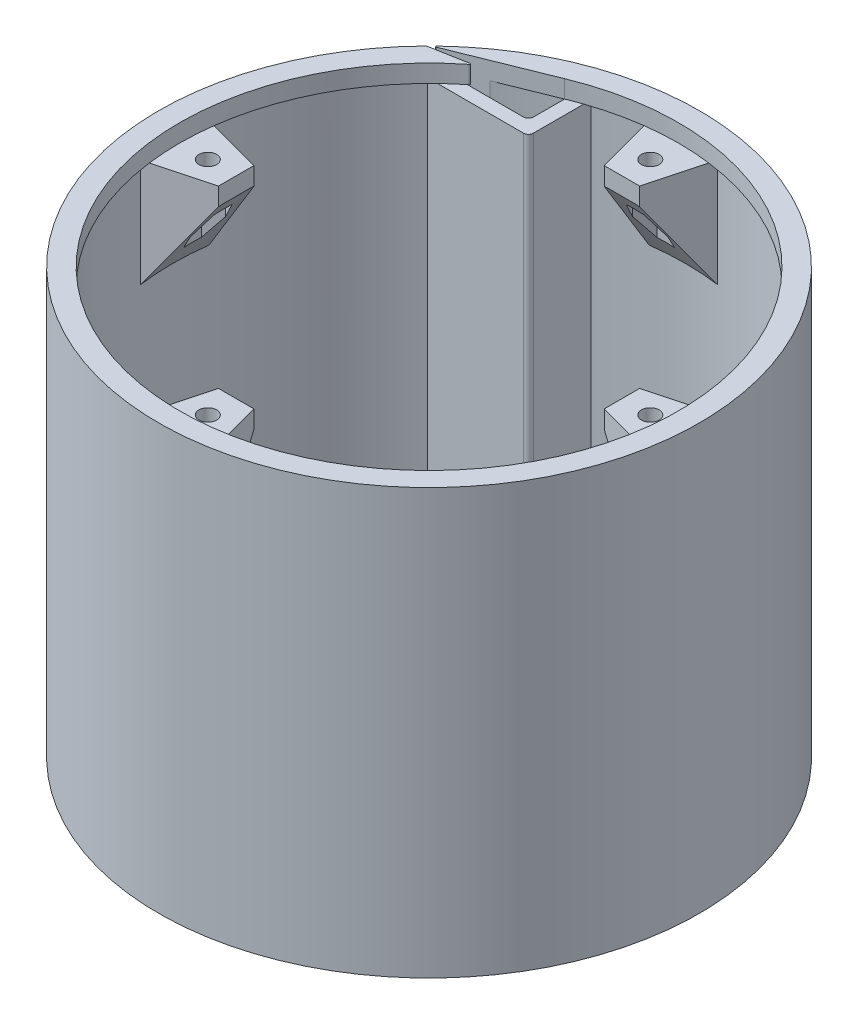
SolidWorks part; units mm, degrees
ref_plane "Front Plane" through (0, 0, 0) normal (0, 0, 1) x (1, 0, 0)
ref_plane "Top Plane" through (0, 0, 0) normal (0, 1, 0) x (1, 0, 0)
ref_plane "Right Plane" through (0, 0, 0) normal (1, 0, 0) x (0, 0, -1)
sketch "Sketch1" plane through (0, 0, 0) normal (0, 1, 0) x (1, 0, 0)
  line L0 (0, 0) -> (0, 89.535) construction
  circle A0 centre (0, 0) radius 89.535
  circle A1 centre (0, 79.375) radius 3.175
  circle A2 centre (20.5438, 76.6704) radius 3.175
  circle A3 centre (39.6875, 68.7408) radius 3.175 [skipped]
  circle A4 centre (56.1266, 56.1266) radius 3.175 [skipped]
  circle A5 centre (68.7408, 39.6875) radius 3.175 [skipped]
  circle A6 centre (76.6704, 20.5438) radius 3.175
  circle A7 centre (79.375, 0) radius 3.175
  circle A8 centre (76.6704, -20.5438) radius 3.175
  circle A9 centre (68.7408, -39.6875) radius 3.175 [skipped]
  circle A10 centre (56.1266, -56.1266) radius 3.175 [skipped]
  circle A11 centre (39.6875, -68.7408) radius 3.175 [skipped]
  circle A12 centre (20.5438, -76.6704) radius 3.175
  circle A13 centre (0, -79.375) radius 3.175
  circle A14 centre (-20.5438, -76.6704) radius 3.175
  circle A15 centre (-39.6875, -68.7408) radius 3.175 [skipped]
  circle A16 centre (-56.1266, -56.1266) radius 3.175 [skipped]
  circle A17 centre (-68.7408, -39.6875) radius 3.175 [skipped]
  circle A18 centre (-76.6704, -20.5438) radius 3.175
  circle A19 centre (-79.375, 0) radius 3.175
  circle A20 centre (-76.6704, 20.5438) radius 3.175
  circle A21 centre (-68.7408, 39.6875) radius 3.175 [skipped]
  circle A22 centre (-56.1266, 56.1266) radius 3.175 [skipped]
  circle A23 centre (-39.6875, 68.7408) radius 3.175 [skipped]
  circle A24 centre (-20.5438, 76.6704) radius 3.175
  circle A25 centre (0, 0) radius 97.0209
  circle A26 centre (0, 0) radius 92.0209
  point P55 (0, 0)
  dimension "D1" = 179.07
  dimension "D2" = 6.35
  dimension "D3" = 79.375
  dimension "D4" = 24
  dimension "D5" = 194.0417
  dimension "D6" = 5
extrude "Boss-Extrude1" add sketch "Sketch1" along normal blind 152.4 contours A25 A26
sketch "Sketch2" plane through (0, 152.4, 0) normal (0, 1, 0) x (1, 0, 0)
  circle A1 centre (0, 0) radius 92.0209
  circle A2 centre (0, 0) radius 92.0209
  circle A3 centre (0, 0) radius 97.0209
  circle A4 centre (0, 0) radius 97.0209
  circle A5 centre (20.5438, 76.6704) radius 3.175
  circle A6 centre (20.5438, 76.6704) radius 3.175
  circle A7 centre (0, 79.375) radius 3.175
  circle A8 centre (0, 79.375) radius 3.175
  circle A9 centre (0, 0) radius 89.535
  circle A10 centre (0, 0) radius 89.535
  circle A11 centre (20.5438, -76.6704) radius 3.175
  circle A12 centre (20.5438, -76.6704) radius 3.175
  circle A13 centre (76.6704, -20.5438) radius 3.175
  circle A14 centre (76.6704, -20.5438) radius 3.175
  circle A15 centre (79.375, 0) radius 3.175
  circle A16 centre (79.375, 0) radius 3.175
  circle A17 centre (76.6704, 20.5438) radius 3.175
  circle A18 centre (76.6704, 20.5438) radius 3.175
  circle A19 centre (-76.6704, 20.5438) radius 3.175
  circle A20 centre (-76.6704, 20.5438) radius 3.175
  circle A21 centre (-79.375, 0) radius 3.175
  circle A22 centre (-79.375, 0) radius 3.175
  circle A23 centre (-76.6704, -20.5438) radius 3.175
  circle A24 centre (-76.6704, -20.5438) radius 3.175
  circle A25 centre (-20.5438, -76.6704) radius 3.175
  circle A26 centre (-20.5438, -76.6704) radius 3.175
  circle A27 centre (0, -79.375) radius 3.175
  circle A28 centre (0, -79.375) radius 3.175
  circle A29 centre (-20.5438, 76.6704) radius 3.175
  circle A30 centre (-20.5438, 76.6704) radius 3.175
  circle M16 centre (0, 0) radius 92.0209
  dimension "D1" = 0
  dimension "D2" = 0
  dimension "D3" = 0
  dimension "D4" = 0
  dimension "D5" = 0
  dimension "D6" = 0
  dimension "D7" = 0
  dimension "D8" = 0
  dimension "D9" = 0
  dimension "D10" = 0
  dimension "D11" = 0
  dimension "D12" = 0
  dimension "D13" = 0
  dimension "D14" = 0
  dimension "D15" = 0
extrude "Boss-Extrude2" add sketch "Sketch2" against normal blind 6.35 contours A10 M16
sketch "Sketch3" plane through (0, 146.05, 0) normal (0, -1, 0) x (1, 0, 0)
  line L0 (0, 89.535) -> (0, 0) construction
  line L1 (-6.35, 69.215) -> (6.35, 69.215)
  line L2 (-12.2417, 91.203) -> (-6.35, 69.215)
  line L3 (6.35, 69.215) -> (12.2417, 91.203)
  circle A1 centre (0, 0) radius 92.0209
  circle A2 centre (0, 0) radius 92.0209
  circle A3 centre (0, 0) radius 97.0209
  circle A4 centre (0, 0) radius 97.0209
  circle A5 centre (20.5438, -76.6704) radius 3.175
  circle A6 centre (20.5438, -76.6704) radius 3.175
  circle A7 centre (0, -79.375) radius 3.175
  circle A8 centre (0, -79.375) radius 3.175
  circle A9 centre (0, 0) radius 89.535
  circle A10 centre (0, 0) radius 89.535
  circle A11 centre (20.5438, 76.6704) radius 3.175
  circle A12 centre (20.5438, 76.6704) radius 3.175
  circle A13 centre (76.6704, 20.5438) radius 3.175
  circle A14 centre (76.6704, 20.5438) radius 3.175
  circle A15 centre (79.375, 0) radius 3.175
  circle A16 centre (79.375, 0) radius 3.175
  circle A17 centre (76.6704, -20.5438) radius 3.175
  circle A18 centre (76.6704, -20.5438) radius 3.175
  circle A19 centre (-76.6704, -20.5438) radius 3.175
  circle A20 centre (-76.6704, -20.5438) radius 3.175
  circle A21 centre (-79.375, 0) radius 3.175
  circle A22 centre (-79.375, 0) radius 3.175
  circle A23 centre (-76.6704, 20.5438) radius 3.175
  circle A24 centre (-76.6704, 20.5438) radius 3.175
  circle A25 centre (-20.5438, 76.6704) radius 3.175
  circle A26 centre (-20.5438, 76.6704) radius 3.175
  circle A27 centre (0, 79.375) radius 3.175
  circle A28 centre (0, 79.375) radius 3.175
  circle A29 centre (-20.5438, -76.6704) radius 3.175
  circle A30 centre (-20.5438, -76.6704) radius 3.175
  circle M20 centre (0, 0) radius 89.535
  circle M21 centre (0, 0) radius 92.0209
  dimension "D16" = 12.7
  dimension "D17" = 6.35
  dimension "D18" = 20.32
  dimension "D19" = 15
  dimension "D20" = 15
  dimension "D1" = 0
  dimension "D2" = 0
  dimension "D3" = 0
  dimension "D4" = 0
  dimension "D5" = 0
  dimension "D6" = 0
  dimension "D7" = 0
  dimension "D8" = 0
  dimension "D9" = 0
  dimension "D10" = 0
  dimension "D11" = 0
  dimension "D12" = 0
  dimension "D13" = 0
  dimension "D14" = 0
  dimension "D15" = 0
extrude "Boss-Extrude3" add sketch "Sketch3" along normal blind 6.35 contours A10 L3 L2 M20 M21 | L0 L2 L1 A28 M20 | A10 L0 A28 L1 L3
pattern_circular "CirPattern1" count 4 every 90 about axis through (0, 0, 0) along (0, 1, 0) of "Boss-Extrude3"
sketch "Sketch4" plane through (0, 0, 0) normal (0, -1, 0) x (1, 0, 0)
  line L0 (0, 0) -> (0, 97.0209) construction
  line L1 (7.62, 96.7212) -> (7.62, 0)
  line L2 (7.62, 0) -> (-7.62, 0)
  line L3 (-7.62, 0) -> (-7.62, 96.7212)
  line L4 (0, 7.62) -> (96.7212, 7.62)
  line L5 (96.7212, -7.62) -> (0, -7.62)
  line L6 (0, -7.62) -> (0, 7.62)
  line L7 (7.62, 0) -> (7.62, -96.7212)
  line L8 (-7.62, -96.7212) -> (-7.62, 0)
  line L9 (-7.62, 0) -> (7.62, 0)
  line L10 (0, -7.62) -> (-96.7212, -7.62)
  line L11 (-96.7212, 7.62) -> (0, 7.62)
  line L12 (0, 7.62) -> (0, -7.62)
  circle A0 centre (0, 0) radius 97.0209 construction
  arc A1 (7.62, 96.7212) -> (-7.62, 96.7212) centre (0, 0) ccw
  circle A2 centre (0, 76.2) radius 3.175
  circle A3 centre (0, 38.1) radius 3.175
  arc A4 (96.7212, -7.62) -> (96.7212, 7.62) centre (0, 0) ccw
  circle A5 centre (76.2, 0) radius 3.175
  circle A6 centre (38.1, 0) radius 3.175
  arc A7 (-7.62, -96.7212) -> (7.62, -96.7212) centre (0, 0) ccw
  circle A8 centre (0, -76.2) radius 3.175
  circle A9 centre (0, -38.1) radius 3.175
  arc A10 (-96.7212, 7.62) -> (-96.7212, -7.62) centre (0, 0) ccw
  circle A11 centre (-76.2, 0) radius 3.175
  circle A12 centre (-38.1, 0) radius 3.175
  circle A13 centre (0, 0) radius 3.175
  point P40 (0, 0)
  circle M8 centre (0, 0) radius 92.0209
  dimension "D4" = 6.35
  dimension "D5" = 6.35
  dimension "D6" = 38.1
  dimension "D7" = 76.2
  dimension "D9" = 6.35
  dimension "D1" = 0
  dimension "D2" = 7.62
  dimension "D3" = 15.24
  dimension "D8" = 4
extrude "Boss-Extrude4" add sketch "Sketch4" against normal blind 6.35 contours L0 L4 L1 A2 A3 M8 | L11 L0 A3 A2 L3 M8 | L1 L7 L5 L4 A6 A5 M8 | L5 L10 L8 L7 A9 A8 M8 | L11 L10 L8 L3 A12 A11 M8 | A13 L12 L11 L3 L9 | A13 L2 L1 L4 L12 | A13 L6 L5 L7 L2 | A13 L9 L8 L10 L6
chamfer "Chamfer1" distance 22.606 angle 55 12 edges at (9.2958, 139.7, 80.209) (0, 139.7, 92.0209) (-9.2958, 139.7, 80.209) (80.209, 139.7, -9.2958) (92.0209, 139.7, 0) (80.209, 139.7, 9.2958) (-9.2958, 139.7, -80.209) (0, 139.7, -92.0209) (9.2958, 139.7, -80.209) (-80.209, 139.7, 9.2958) (-92.0209, 139.7, 0) (-80.209, 139.7, -9.2958)
ref_plane "Plane1" through (0, 139.7, 0) normal (0, 1, 0) x (1, 0, 0)
sketch "Sketch5" plane through (0, 139.7, 0) normal (0, 1, 0) x (1, 0, 0)
  line L1 (-73.875, 3.1754) -> (-79.375, 6.3509)
  line L2 (-79.375, 6.3509) -> (-84.875, 3.1754)
  line L3 (-84.875, 3.1754) -> (-84.875, -3.1754)
  line L4 (-84.875, -3.1754) -> (-79.375, -6.3509)
  line L5 (-79.375, -6.3509) -> (-73.875, -3.1754)
  line L6 (-73.875, -3.1754) -> (-73.875, 3.1754)
  circle A1 centre (-79.375, 0) radius 5.5 construction
  dimension "D1" = 11
extrude "Cut-Extrude1" cut sketch "Sketch5" against normal blind 25.4
pattern_circular "CirPattern2" count 4 over 360 about axis through (0, 0, 0) along (0, 1, 0) of "Cut-Extrude1"
sketch "Sketch12" plane through (0, 152.4, 0) normal (0, 1, 0) x (1, 0, 0)
  line L0 (0, 0) -> (0, 97.0209) construction
  line L1 (0, 0) -> (-68.6041, 68.6041) construction
  line L2 (-68.1536, 69.0516) -> (-32.8194, 83.3031)
  line L3 (-69.0516, 68.1536) -> (-54.8919, 70.7347)
  circle A0 centre (0, 0) radius 97.0209 construction
  circle A1 centre (0, 0) radius 89.535 construction
  circle A2 centre (0, 0) radius 97.0209
  circle A3 centre (0, 0) radius 97.0209
  circle M6 centre (0, 0) radius 97.0209
  circle M7 centre (0, 0) radius 89.535
  dimension "D1" = 45
  dimension "D3" = 0.635
  dimension "D4" = 0.635
  dimension "D5" = 38.1
  dimension "D6" = 25.4
  dimension "D2" = 0
extrude "Cut-Extrude6" cut sketch "Sketch12" against normal up to surface (152.4 mm away) contours L3 L2 M6 M7
fillet "Fillet2" radius 0.254 4 edges at (-69.0516, 76.2, -68.1536) (-68.1536, 76.2, -69.0516) (-54.8919, 149.225, -70.7347) (-53.2033, 73.025, -75.0816)
sketch "Sketch13" plane through (0, 152.4, 0) normal (0, 1, 0) x (1, 0, 0)
  line L0 (-34.1601, 82.7623) -> (-34.1601, 85.4454)
  line L1 (-34.1601, 82.7623) -> (-34.1601, 69.8126)
  line L2 (-34.1601, 69.8126) -> (-59.9503, 69.8126)
  line L3 (-65.3235, 64.8126) -> (-29.1601, 64.8126)
  line L4 (-29.1601, 64.8126) -> (-29.1601, 87.2784)
  arc A0 (-12.2417, 91.203) -> (-53.1791, 75.0987) centre (0, 0) ccw construction
  arc A1 (-59.9503, 69.8126) -> (-91.203, 12.2417) centre (0, 0) ccw construction
  arc A2 (-59.9503, 69.8126) -> (-91.203, 12.2417) centre (0, 0) ccw
  arc A3 (-12.2417, 91.203) -> (-53.1791, 75.0987) centre (0, 0) ccw
  point P0 (-34.1601, 82.7623)
  point P1 (-59.9503, 69.8126)
  arc M3 (-34.1601, 82.7623) -> (-55.6977, 70.1019) centre (0, 0) cw
  dimension "D1" = 5
  dimension "D2" = 5
extrude "Boss-Extrude5" add sketch "Sketch13" against normal up to surface (152.4 mm away) contours L3 L4 L1 L2 M3 | L4 A3 L0 M3 | L2 A2 L3 M3 up to face at (-76.2, 0, -3.175)
sketch "Sketch14" plane through (0, 152.4, 0) normal (0, 1, 0) x (1, 0, 0)
  line L4 (-55.9013, 70.5507) -> (-68.9727, 68.168)
  line L5 (-66.9573, 69.5342) -> (-34.1601, 82.7623)
  line L6 (-34.1601, 82.7623) -> (-34.1601, 69.8126)
  line L7 (-34.1601, 69.8126) -> (-56.0599, 69.8126)
  line L8 (-55.9013, 70.5507) -> (-68.9727, 68.168)
  line L9 (-66.9573, 69.5342) -> (-34.1601, 82.7623)
  line L10 (-34.1601, 82.7623) -> (-34.1601, 69.8126)
  line L11 (-34.1601, 69.8126) -> (-56.0599, 69.8126)
  circle A0 centre (0, 0) radius 89.535
  arc A5 (-55.6977, 70.1019) -> (-55.9013, 70.5507) centre (-55.8557, 70.3008) ccw
  arc A6 (-55.6977, 70.1019) -> (-55.9013, 70.5507) centre (-55.8557, 70.3008) ccw
  arc A7 (-69.1081, 68.0964) -> (-67.2283, 69.9529) centre (0, 0) ccw
  arc A8 (-68.9727, 68.168) -> (-69.1081, 68.0964) centre (-68.9271, 67.9181) ccw
  arc A9 (-55.6977, 70.1019) -> (-56.0599, 69.8126) centre (0, 0) ccw
  arc A12 (-69.1081, 68.0964) -> (-67.2283, 69.9529) centre (0, 0) ccw
  arc A14 (-55.6977, 70.1019) -> (-56.0599, 69.8126) centre (0, 0) ccw
  arc A15 (-68.9727, 68.168) -> (-69.1081, 68.0964) centre (-68.9271, 67.9181) ccw
  arc A16 (-67.2283, 69.9529) -> (-66.9573, 69.5342) centre (-67.0523, 69.7697) ccw
  arc A17 (-67.2283, 69.9529) -> (-66.9573, 69.5342) centre (-67.0523, 69.7697) ccw
  line M11 (-61.7725, 64.8126) -> (-29.1601, 64.8126)
  line M12 (-29.1601, 64.8126) -> (-29.1601, 84.6534)
  line M19 (-34.1601, 82.7623) -> (-34.1601, 69.8126)
  line M20 (-34.1601, 69.8126) -> (-56.0599, 69.8126)
  dimension "D1" = 0
extrude "Cut-Extrude8" cut sketch "Sketch14" against normal blind 6.35 contours A0 M12 M19 M20 M11
fillet "Fillet3" radius 1.778 3 edges at (-34.1601, 73.025, -85.4454) (-34.1601, 73.025, -69.8126) (-29.1601, 73.025, -64.8126)
